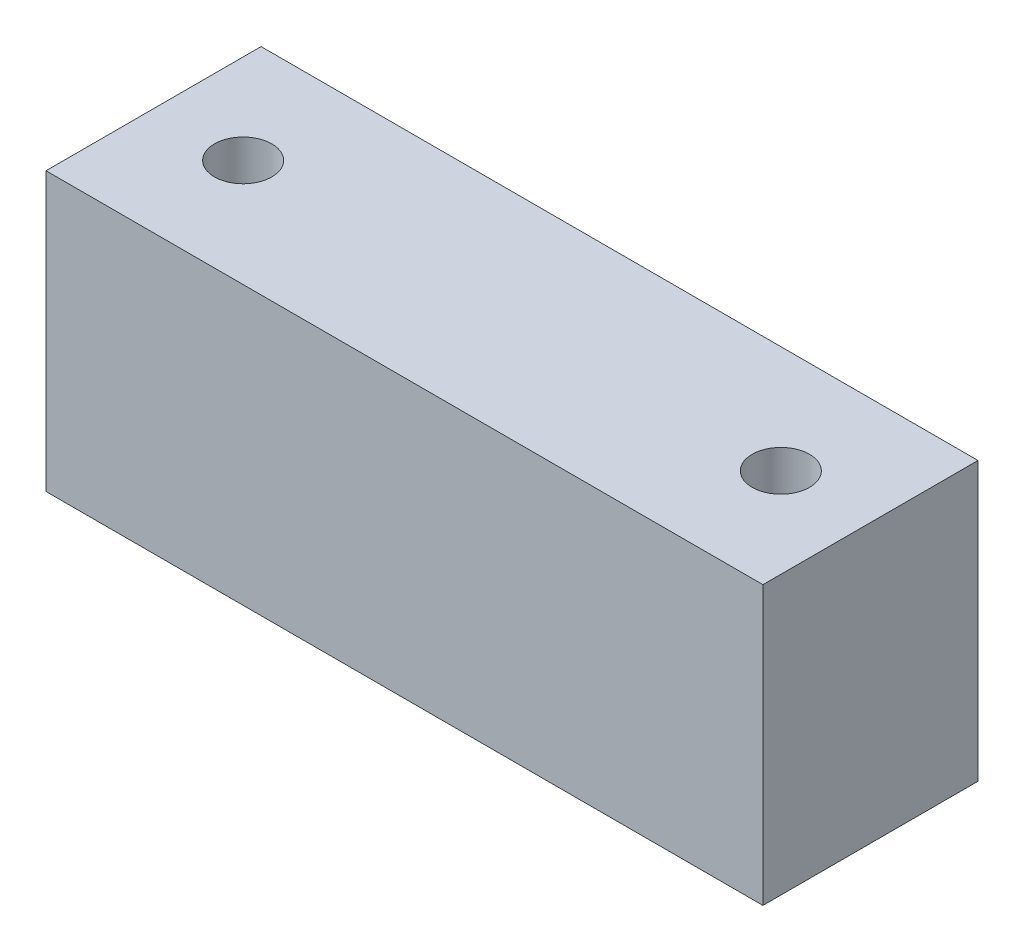
SolidWorks part; units mm, degrees
ref_plane "Front Plane" through (0, 0, 0) normal (0, 0, 1) x (1, 0, 0)
ref_plane "Top Plane" through (0, 0, 0) normal (0, 1, 0) x (1, 0, 0)
ref_plane "Right Plane" through (0, 0, 0) normal (1, 0, 0) x (0, 0, -1)
sketch "Sketch1" plane through (0, 0, 0) normal (0, 1, 0) x (1, 0, 0)
  line L1 (-20, 6) -> (20, 6)
  line L2 (-20, 6) -> (-20, -6)
  line L3 (-20, -6) -> (20, -6)
  line L4 (20, 6) -> (20, -6)
  line L5 (-20, 6) -> (20, -6) construction
  line L6 (-20, -6) -> (20, 6) construction
  point P0 (0, 0)
  dimension "D1" = 40
  dimension "D2" = 12
extrude "Boss-Extrude1" add sketch "Sketch1" along normal blind 15.5
sketch "Sketch2" plane through (0, 15.5, 0) normal (0, 1, 0) x (1, 0, 0)
  line L0 (-20, 0) -> (20, 0) construction
  line L1 (-20, 6) -> (-20, -6) construction
  line L2 (20, -6) -> (20, 6) construction
  line L3 (0, -6) -> (0, 7.5) construction
  line L4 (-20, -6) -> (20, -6) construction
  line L5 (20, 6) -> (-20, 6) construction
  circle A0 centre (15, 0) radius 1.6
  circle A1 centre (-15, 0) radius 1.6
  point P17 (0, 6)
  dimension "D1" = 3.2
  dimension "D2" = 15
extrude "Cut-Extrude2" cut sketch "Sketch2" against normal through all
sketch "Sketch3" plane through (-20, 0, 0) normal (-1, 0, 0) x (0, 0, 1)
  line L0 (-5.25, 15.5) -> (-5.25, 14.5)
  line L1 (-6, 15.5) -> (6, 15.5) construction
  line L2 (-5.25, 14.5) -> (-4.25, 14.5)
  line L3 (-4.25, 14.5) -> (-4.25, 15.5)
  line L4 (-4.25, 15.5) -> (-5.25, 15.5)
  line L5 (-3.25, 14.5) -> (-2.25, 14.5)
  line L6 (-3.25, 15.5) -> (-3.25, 14.5)
  line L7 (-2.25, 14.5) -> (-2.25, 15.5)
  line L8 (-2.25, 15.5) -> (-3.25, 15.5)
  line L9 (-1.25, 14.5) -> (-0.25, 14.5)
  line L10 (-1.25, 15.5) -> (-1.25, 14.5)
  line L11 (-0.25, 14.5) -> (-0.25, 15.5)
  line L12 (-0.25, 15.5) -> (-1.25, 15.5)
  line L13 (0.75, 14.5) -> (1.75, 14.5)
  line L14 (0.75, 15.5) -> (0.75, 14.5)
  line L15 (1.75, 14.5) -> (1.75, 15.5)
  line L16 (1.75, 15.5) -> (0.75, 15.5)
  line L17 (2.75, 14.5) -> (3.75, 14.5)
  line L18 (2.75, 15.5) -> (2.75, 14.5)
  line L19 (3.75, 14.5) -> (3.75, 15.5)
  line L20 (3.75, 15.5) -> (2.75, 15.5)
  line L21 (4.75, 14.5) -> (5.75, 14.5)
  line L22 (4.75, 15.5) -> (4.75, 14.5)
  line L23 (5.75, 14.5) -> (5.75, 15.5)
  line L24 (5.75, 15.5) -> (4.75, 15.5)
  line L25 (6.75, 14.5) -> (7.75, 14.5)
  line L26 (6.75, 15.5) -> (6.75, 14.5)
  line L27 (7.75, 14.5) -> (7.75, 15.5)
  line L28 (7.75, 15.5) -> (6.75, 15.5)
  line L29 (8.75, 14.5) -> (9.75, 14.5)
  line L30 (8.75, 15.5) -> (8.75, 14.5)
  line L31 (9.75, 14.5) -> (9.75, 15.5)
  line L32 (9.75, 15.5) -> (8.75, 15.5)
  line L33 (-6, 15.5) -> (-6, 0) construction
  dimension "D1" = 1
  dimension "D3" = 0.75
  dimension "D4" = 1
  dimension "D5" = 1
  dimension "D6" = 1
  dimension "D2" = 8
extrude "Teeth" [suppressed] cut sketch "Sketch3" against normal blind 5 and the other way blind 5 from surface starting at plane "Right Plane"
sketch "Sketch4" [suppressed] plane through (0, 5, 0) normal (0, 1, 0) x (1, 0, 0)
  line L0 (-15, 0) -> (-15, 3.4641) construction
  line L1 (-15, 3.4641) -> (-18, 1.7321)
  line L2 (-18, 1.7321) -> (-18, -1.7321)
  line L3 (-18, -1.7321) -> (-15, -3.4641)
  line L4 (-15, -3.4641) -> (-12, -1.7321)
  line L5 (-12, -1.7321) -> (-12, 1.7321)
  line L6 (-12, 1.7321) -> (-15, 3.4641)
  line L7 (0, 7.5) -> (0, -7.5) construction
  line L8 (20, 7.5) -> (-20, 7.5) construction
  line L9 (5, -7.5) -> (-5, -7.5) construction
  line L10 (15, 0) -> (15, 3.4641) construction
  line L11 (12, 1.7321) -> (15, 3.4641)
  line L12 (12, -1.7321) -> (12, 1.7321)
  line L13 (15, -3.4641) -> (12, -1.7321)
  line L14 (18, -1.7321) -> (15, -3.4641)
  line L15 (18, 1.7321) -> (18, -1.7321)
  line L16 (15, 3.4641) -> (18, 1.7321)
  line L17 (-15, 0) -> (-15, 3.4641) construction
  circle A0 centre (-15, 0) radius 3 construction
  circle A1 centre (15, 0) radius 3 construction
  dimension "D1" = 6
extrude "Cut-Extrude4" [suppressed] cut sketch "Sketch4" against normal blind 2
equation "\"X-ROD-SPACING\"=45"
equation "\"Y-ROD-SPACING\"=75"
equation "\"Z-ROD-SPACING\"=17.5"
equation "\"Y-BED-OFFSET\"=2"
equation "\"Y-BED-ROD-INSET\"=3.5"
equation "\"T-SLOT-NUT-FILLET-RADIUS\"=0.25"
equation "\"T-SLOT-SCREW-SHAFT-RADIUS\"=1.75"
equation "\"T-SLOT-SCREW-SHAFT-CUTOUT-LENGTH\"=10.5"
equation "\"T-SLOT-NUT-DEPTH\"=4.2"
equation "\"T-SLOT-NUT-WIDTH\"=3"
equation "\"T-SLOT-NUT-END-DISTANCE\"=8"
equation "\"ACRYLIC-THICKNESS\"=10"
equation "\"ACRYLIC-THICKNESS2\"=4.5"
equation "\"ACRYLIC-TAB-CUTOUT-SIZE\"=\"ACRYLIC-THICKNESS\"+\"ACRYLIC-TAB-TOLERANCE\"*2"
equation "\"ACRYLIC-TAB-WIDTH\"=\"ACRYLIC-THICKNESS\""
equation "\"ACRYLIC-M3-HOLE\"=3.2"
equation "\"SMOOTHROD-CAP-SCREW-DISTANCE\"=20"
equation "\"FRAME-WIDTH-INNER\"=370"
equation "\"NEMA17-HOLE-SPACING\"=31"
equation "\"NEMA17-CENTRAL-CUTOUT\"=22.5"
equation "\"Z-BRACKET-REACH\"=55"
equation "\"TOP-BRACKET-SPACING\"=40"
equation "\"SMOOTHROD-X-LENGTH\"=350"
equation "\"SMOOTHROD-Y-LENGTH\"=350"
equation "\"SMOOTHROD-Z-LENGTH\"=350"
equation "\"SMOOTHROD-TIGHTENING-HEADROOM\"=1"
equation "\"LEADSCREW-Z-LENGTH\"=300"
equation "\"SCREW-LENGTH-FRAME\"=\"ACRYLIC-THICKNESS\" + 10"
equation "\"SCREW-HEAD-RADIUS\"=6"
equation "\"PRINTED-X-SMOOTHROD-DIAMETER\"=8.2"
equation "\"PRINTED-X-SMOOTHROD-CUTOUT\"=10"
equation "\"PRINTED-X-BASE-HEIGHT\"=10"
equation "\"PRINTED-LM8UU-CUTOUT-SIZE\"=15.25"
equation "\"PRINTED-LM8UU-CUTOUT-LENGTH\"=24.5"
equation "\"PRINTED-X-IDLER-HEIGHT\"=16"
equation "\"PSU-MOUNTING-WIDTH\"=95"
equation "\"PSU-MOUNTING-HEIGHT\"=177"
equation "\"Y-BELT-TO-ROD-DISTANCE\"=20"
equation "\"D1@Sketch4\"=\"T-SLOT-NUT-WIDTH\"*2"
